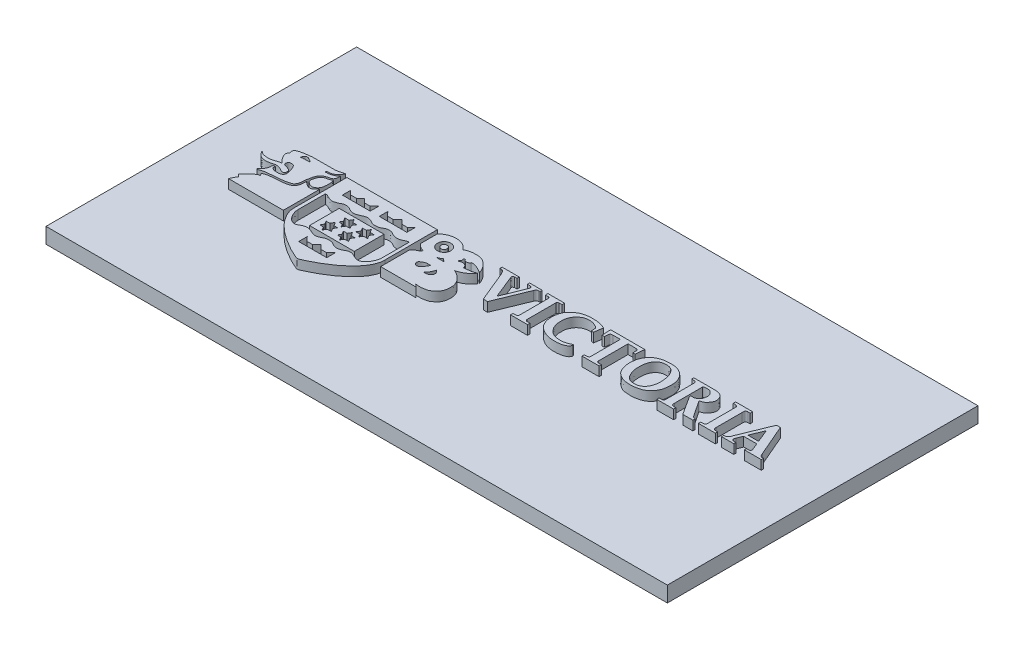
SolidWorks part; units mm, degrees
ref_plane "Front Plane" through (0, 0, 0) normal (0, 0, 1) x (1, 0, 0)
ref_plane "Top Plane" through (0, 0, 0) normal (0, 1, 0) x (1, 0, 0)
ref_plane "Right Plane" through (0, 0, 0) normal (1, 0, 0) x (0, 0, -1)
sketch "Sketch1" plane through (0, 0, 0) normal (0, 1, 0) x (1, 0, 0)
  line L1 (-100, 50) -> (100, 50)
  line L2 (-100, 50) -> (-100, -50)
  line L3 (-100, -50) -> (100, -50)
  line L4 (100, 50) -> (100, -50)
  dimension "D1" = 100
  dimension "D2" = 200
  dimension "D3" = 50
  dimension "D4" = 100
extrude "Boss-Extrude1" add sketch "Sketch1" along normal blind 5
sketch "Sketch3" plane through (0, 5, 0) normal (0, 1, 0) x (1, 0, 0)
  line L0 (337.3172, 310.4568) -> (1593.3172, 310.4568) construction
  line L2 (214, 281.56) -> (1470, 281.56) construction
sketch "Sketch4" plane through (0, 5, 0) normal (0, 1, 0) x (1, 0, 0)
sketch "Sketch5" plane through (0, 5, 0) normal (0, 1, 0) x (1, 0, 0)
  line L0 (-63.2832, 1.3739) -> (-63.2832, -10.3111)
  line L1 (-63.2832, -10.3111) -> (-80.9037, -10.3111)
  line L2 (-62.2093, 9.0496) -> (-33.087, 9.0496)
  line L3 (-33.087, 9.0496) -> (-33.087, -7.8265)
  line L4 (-62.2093, 9.0496) -> (-62.2093, -7.8265)
  line L5 (-52.1107, -16.5513) -> (-52.1107, -13.7896)
  line L6 (-52.1107, -13.7896) -> (-50.8663, -15.1704)
  line L7 (-50.8663, -15.1704) -> (-49.0633, -15.1704)
  line L8 (-49.0633, -15.1704) -> (-47.6668, -13.7739)
  line L9 (-47.6668, -13.7739) -> (-46.2702, -15.1704)
  line L10 (-46.2702, -15.1704) -> (-44.4842, -15.1704)
  line L11 (-44.4842, -15.1704) -> (-43.0876, -13.7739)
  line L12 (-43.0876, -13.7739) -> (-43.0876, -16.5513)
  line L13 (-43.0876, -16.5513) -> (-52.1107, -16.5513)
  line L14 (-51.5411, -5.2897) -> (-52.1934, -6.4621)
  line L15 (-53.3409, -8.5244) -> (-52.1596, -8.5244)
  line L16 (-49.6492, -8.5244) -> (-50.261, -7.4783)
  line L17 (-53.3409, -6.4621) -> (-52.1934, -6.4621)
  line L18 (-49.6492, -6.4621) -> (-50.261, -7.4783)
  line L19 (-51.5411, -9.6043) -> (-52.1596, -8.5244)
  line L20 (-50.8554, -6.4621) -> (-49.6492, -6.4621)
  line L21 (-52.7588, -7.4783) -> (-53.3409, -8.5244)
  line L22 (-52.7588, -7.4783) -> (-53.3409, -6.4621)
  line L23 (-50.8909, -8.5244) -> (-49.6492, -8.5244)
  line L24 (-50.8554, -6.4621) -> (-51.5411, -5.2897)
  line L25 (-50.8909, -8.5244) -> (-51.5411, -9.6043)
  line L26 (-47.8046, -6.4621) -> (-46.5759, -6.4621)
  line L27 (-44.1019, -6.4621) -> (-44.7111, -7.482)
  line L28 (-45.9533, -9.5616) -> (-46.5727, -8.5244)
  line L29 (-45.9533, -5.3563) -> (-46.5759, -6.4621)
  line L30 (-47.7371, -8.5244) -> (-46.5727, -8.5244)
  line L31 (-44.1019, -8.5244) -> (-44.7111, -7.482)
  line L32 (-45.307, -6.4621) -> (-44.1019, -6.4621)
  line L33 (-47.1721, -7.521) -> (-47.7371, -8.5244)
  line L34 (-47.1721, -7.521) -> (-47.8046, -6.4621)
  line L35 (-45.3338, -8.5244) -> (-44.1019, -8.5244)
  line L36 (-45.3338, -8.5244) -> (-45.9533, -9.5616)
  line L37 (-45.307, -6.4621) -> (-45.9533, -5.3563)
  line L38 (-49.3065, -1.5215) -> (-49.8917, -2.5463)
  line L39 (-51.0871, -4.64) -> (-49.9803, -4.64)
  line L40 (-47.4661, -4.64) -> (-48.0944, -3.5753)
  line L41 (-51.2589, -2.5463) -> (-49.8917, -2.5463)
  line L42 (-47.4661, -2.5463) -> (-48.0944, -3.5753)
  line L43 (-49.3625, -5.6517) -> (-49.9803, -4.64)
  line L44 (-48.7017, -2.5463) -> (-47.4661, -2.5463)
  line L45 (-50.5523, -3.7034) -> (-51.0871, -4.64)
  line L46 (-50.5523, -3.7034) -> (-51.2589, -2.5463)
  line L47 (-48.7446, -4.64) -> (-47.4661, -4.64)
  line L48 (-48.7446, -4.64) -> (-49.3625, -5.6517)
  line L49 (-48.7017, -2.5463) -> (-49.3065, -1.5215)
  line L50 (-45.6097, -4.64) -> (-44.975, -3.5824)
  line L51 (-43.7381, -1.5215) -> (-43.1103, -2.5463)
  line L52 (-41.8277, -4.64) -> (-43.1226, -4.64)
  line L53 (-45.6097, -2.5463) -> (-44.975, -3.5824)
  line L54 (-43.7187, -5.6332) -> (-43.1226, -4.64)
  line L55 (-41.866, -2.5463) -> (-43.1103, -2.5463)
  line L56 (-44.3272, -4.64) -> (-43.7187, -5.6332)
  line L57 (-44.3531, -2.5463) -> (-43.7381, -1.5215)
  line L58 (-44.3531, -2.5463) -> (-45.6097, -2.5463)
  line L59 (-42.4818, -3.5723) -> (-41.8277, -4.64)
  line L60 (-42.4818, -3.5723) -> (-41.866, -2.5463)
  line L61 (-44.3272, -4.64) -> (-45.6097, -4.64)
  line L62 (-34.1334, 1.0615) -> (-34.1334, -7.8265)
  line L63 (-54.827, -0.8011) -> (-40.4157, -0.8011)
  line L64 (-54.827, -0.8011) -> (-54.827, -10.3593)
  line L65 (-54.827, -10.3593) -> (-40.4157, -10.3593)
  line L66 (-40.4157, -0.8011) -> (-40.4157, -10.3593)
  line L67 (-61.1063, 1.0449) -> (-61.1063, -7.8265)
  line L68 (-58.0074, 3.4152) -> (-49.0633, 3.4152)
  line L69 (-49.0633, 3.4152) -> (-49.0633, 6.1619)
  line L70 (-49.0633, 6.1619) -> (-50.4367, 4.7885)
  line L71 (-50.4367, 4.7885) -> (-52.1934, 4.7885)
  line L72 (-52.1934, 4.7885) -> (-53.5353, 6.1305)
  line L73 (-53.5353, 6.1305) -> (-54.8773, 4.7885)
  line L74 (-54.8773, 4.7885) -> (-56.7252, 4.7885)
  line L75 (-56.7252, 4.7885) -> (-58.0074, 6.0706)
  line L76 (-58.0074, 6.0706) -> (-58.0074, 3.4152)
  line L77 (-46.1397, 6.1619) -> (-46.1397, 3.4152)
  line L78 (-46.1397, 3.4152) -> (-37.2605, 3.4152)
  line L79 (-37.2605, 3.4152) -> (-37.2605, 6.1619)
  line L80 (-37.2605, 6.1619) -> (-38.5572, 4.8651)
  line L81 (-38.5572, 4.8651) -> (-40.3517, 4.8651)
  line L82 (-40.3517, 4.8651) -> (-41.7001, 6.2135)
  line L83 (-41.7001, 6.2135) -> (-43.1103, 4.8033)
  line L84 (-43.1103, 4.8033) -> (-44.8724, 4.8033)
  line L85 (-44.8724, 4.8033) -> (-46.1397, 6.1619)
  line L86 (-31.9218, 7.7833) -> (-31.9218, 2.5651)
  line L87 (-31.9218, -10.3593) -> (-20.5485, -10.3593)
  line L88 (-31.9218, -0.9593) -> (-31.9218, -10.3593)
  line L89 (-25.5083, 1.1635) -> (-22.9705, 1.1635)
  line L90 (-25.2779, -1.9652) -> (-24.1564, -1.9652)
  line L91 (-12.2253, 9.0496) -> (-6.6902, 9.0496)
  line L92 (0.6832, 9.0496) -> (0.6832, 8.3375)
  line L93 (0.6832, 8.3375) -> (0.1855, 8.3375)
  line L94 (-12.2253, 8.3375) -> (-12.2253, 9.0496)
  line L95 (-6.6902, 9.0496) -> (-6.6902, 8.3375)
  line L96 (-3.3772, 9.0496) -> (-3.3772, 8.3375)
  line L97 (-3.3772, 9.0496) -> (0.6832, 9.0496)
  line L98 (-6.6902, 8.3375) -> (-7.4716, 8.3375)
  line L99 (-6.3278, -2.896) -> (-4.9619, -2.896)
  line L100 (-4.9619, -2.896) -> (-0.6788, 7.5455)
  line L101 (-6.3278, -2.896) -> (-10.4507, 7.0158)
  line L102 (-4.9331, 0.0557) -> (-2.014, 7.3165)
  line L103 (-4.9331, 0.0557) -> (-7.8598, 7.3165)
  line L104 (-11.6908, 8.3375) -> (-12.2253, 8.3375)
  line L105 (-2.3592, 8.3375) -> (-3.3772, 8.3375)
  line L106 (6.9917, -2.1108) -> (7.904, -2.1108)
  line L107 (6.8779, 8.242) -> (7.904, 8.242)
  line L108 (3.9499, -1.5215) -> (3.9499, 7.7833)
  line L109 (21.0472, 8.3851) -> (20.6035, 5.5732)
  line L110 (6.3721, -1.5215) -> (6.3721, 7.7833)
  line L111 (2.428, -2.896) -> (7.904, -2.896)
  line L112 (2.428, -2.896) -> (2.428, -2.1108)
  line L113 (2.428, -2.1108) -> (3.3607, -2.1108)
  line L114 (7.904, -2.896) -> (7.904, -2.1108)
  line L115 (2.5079, 9.0496) -> (7.904, 9.0496)
  line L116 (2.5079, 9.0496) -> (2.5079, 8.242)
  line L117 (2.5079, 8.242) -> (3.53, 8.242)
  line L118 (7.904, 9.0496) -> (7.904, 8.242)
  line L119 (20.6035, 5.5732) -> (19.925, 5.6803)
  line L120 (19.925, 5.6803) -> (19.8426, 7.0158)
  line L121 (26.9382, 7.9312) -> (24.5244, 7.9312)
  line L122 (25.4187, -2.896) -> (30.9293, -2.896)
  line L123 (25.4187, -2.896) -> (25.4187, -2.1826)
  line L124 (25.4187, -2.1826) -> (25.9053, -2.1826)
  line L125 (30.9293, -2.896) -> (30.9293, -2.1826)
  line L126 (49.4918, 9.0496) -> (49.4918, 8.3851)
  line L127 (29.4217, -1.5215) -> (29.4217, 7.9312)
  line L128 (29.9849, -2.1826) -> (30.9293, -2.1826)
  line L129 (26.9382, -1.5215) -> (26.9382, 7.9312)
  line L130 (29.4217, 7.9312) -> (31.9328, 7.9312)
  line L131 (22.6804, 9.0496) -> (33.7049, 9.0496)
  line L132 (22.6804, 9.0496) -> (22.8673, 6.1619)
  line L133 (22.8673, 6.1619) -> (23.6161, 6.1619)
  line L134 (33.7049, 9.0496) -> (33.4622, 6.1619)
  line L135 (33.4622, 6.1619) -> (32.7405, 6.1619)
  line L136 (49.4918, 9.0496) -> (56.4225, 9.0496)
  line L137 (53.4504, 7.8779) -> (53.4504, -1.1515)
  line L138 (51.0008, -1.2249) -> (51.0008, 7.1755)
  line L139 (57.8954, -2.92) -> (61.1428, -2.92)
  line L140 (49.5337, -2.92) -> (54.9326, -2.92)
  line L141 (49.5337, -2.92) -> (49.5337, -2.1826)
  line L142 (49.5337, -2.1826) -> (50.0195, -2.1826)
  line L143 (54.9326, -2.92) -> (54.9326, -2.1826)
  line L144 (61.1428, -2.92) -> (61.1428, -2.1826)
  line L145 (57.8954, -2.92) -> (54.1811, 2.8405)
  line L146 (57.0409, 2.9956) -> (60.0891, -1.5871)
  line L147 (54.1849, -2.1826) -> (54.9326, -2.1826)
  line L148 (67.6475, 8.2653) -> (68.3886, 8.2653)
  line L149 (62.9361, -2.92) -> (68.3886, -2.92)
  line L150 (62.9361, -2.92) -> (62.9361, -2.1826)
  line L151 (62.9361, -2.1826) -> (63.8006, -2.1826)
  line L152 (68.3886, -2.92) -> (68.3886, -2.1826)
  line L153 (62.9361, 9.0496) -> (68.3886, 9.0496)
  line L154 (62.9361, 9.0496) -> (62.9361, 8.2653)
  line L155 (62.9361, 8.2653) -> (63.6999, 8.2653)
  line L156 (68.3886, 9.0496) -> (68.3886, 8.2653)
  line L157 (67.3329, -2.1826) -> (68.3886, -2.1826)
  line L158 (64.4296, 7.1428) -> (64.4296, -1.2249)
  line L159 (75.871, 5.9878) -> (74.1921, 1.7526)
  line L160 (66.9175, 7.1428) -> (66.9175, -1.2249)
  line L161 (75.871, 5.9878) -> (77.6217, 1.7526)
  line L162 (74.1921, 1.7526) -> (77.6217, 1.7526)
  line L163 (73.8015, 0.7672) -> (78.0291, 0.7672)
  line L164 (77.7139, -2.896) -> (83.1232, -2.896)
  line L165 (77.7139, -2.896) -> (77.7139, -2.2065)
  line L166 (77.7139, -2.2065) -> (78.5421, -2.2065)
  line L167 (83.1232, -2.896) -> (83.1232, -2.2065)
  line L168 (74.2826, -2.896) -> (70.355, -2.896)
  line L169 (74.2826, -2.896) -> (74.2826, -2.2065)
  line L170 (74.2826, -2.2065) -> (73.4593, -2.2065)
  line L171 (70.355, -2.896) -> (70.355, -2.2065)
  line L172 (73.8015, 0.7672) -> (73.1172, -0.9593)
  line L173 (78.0291, 0.7672) -> (78.7977, -1.0923)
  line L174 (76.0075, 9.1296) -> (71.8933, -0.9593)
  line L175 (76.0075, 9.1296) -> (77.2609, 9.1296)
  line L176 (77.2609, 9.1296) -> (81.6634, -1.0923)
  line L177 (70.6873, -2.2065) -> (70.355, -2.2065)
  line L178 (82.7523, -2.2065) -> (83.1232, -2.2065)
  circle A0 centre (-27.1702, 5.3248) radius 2.1439
  circle A1 centre (-27.1725, 5.32) radius 0.9895
  spline S0 degree 3 poles (-63.6706, 9.4448) (-63.3718, 10.0323) (-63.8224, 9.7441) (-64.1106, 9.658) (-64.5317, 9.5574) (-64.9536, 9.4352) (-65.5434, 9.3039) (-66.2489, 9.2125) (-67.1417, 9.2449) (-68.1166, 9.2139) (-69.3679, 9.2331) (-70.6021, 9.2283) (-71.7021, 9.2222) (-72.38, 9.2465) (-73.2805, 9.2286) (-74.4285, 9.1224) (-75.7628, 8.8959) (-76.8244, 8.7102) (-77.5916, 8.4293) (-78.2655, 8.1228) (-78.4173, 7.525) (-78.4231, 7.0723) (-78.239, 6.8794) (-78.1623, 6.7454) (-78.3118, 6.6595) (-78.4554, 6.5414) (-78.5433, 6.3072) (-78.6223, 5.9835) (-78.7042, 5.6314) (-78.6102, 5.2628) (-78.421, 4.8656) (-78.1792, 4.4363) (-77.8669, 3.9347) (-77.5302, 3.4855) (-77.1961, 3.05) (-76.8585, 2.8263) (-76.7231, 2.6634) (-76.5926, 2.6155) (-76.6613, 2.4901) (-76.8004, 2.5711) (-77.0316, 2.5397) (-77.3623, 2.5504) (-77.7564, 2.3515) (-78.1822, 2.2824) (-78.5786, 2.0526) (-79.0593, 1.9753) (-79.6046, 1.7731) (-80.2467, 1.8029) (-80.9206, 1.7931) (-81.4923, 1.8929) (-81.9854, 1.9805) (-82.3592, 2.1503) (-82.6619, 2.3503) (-82.9235, 2.5204) (-83.0259, 2.674) (-83.2103, 2.6978) (-83.1557, 2.5832) (-83.1628, 2.4687) (-83.0084, 2.3856) (-82.9197, 2.2156) (-82.7477, 2.0038) (-82.5121, 1.7498) (-82.2373, 1.4596) (-81.9494, 1.1662) (-81.6102, 1.015) (-81.3149, 0.8302) (-81.0063, 0.7701) (-80.7026, 0.7134) (-80.2979, 0.6377) (-79.72, 0.6349) (-78.9764, 0.7316) (-78.2307, 0.9037) (-77.5321, 1.1317) (-76.8334, 1.2022) (-76.2147, 1.0617) (-75.6858, 0.8931) (-75.2703, 0.6717) (-74.8218, 0.5045) (-74.4906, 0.2282) (-74.1206, 0.2274) (-73.6937, 0.2483) (-73.32, 0.8418) (-73.4364, 1.5648) (-73.9671, 1.9701) (-74.4947, 2.1984) (-75.0734, 2.3775) (-75.5109, 2.4247) (-75.8343, 2.5506) (-75.8972, 2.8252) (-76.0668, 3.0828) (-75.9996, 3.4674) (-75.8109, 3.846) (-75.2643, 4.079) (-74.5597, 4.1038) (-73.9506, 3.6248) (-73.6958, 3.0814) (-73.4593, 2.6057) (-73.3209, 2.1079) (-73.1415, 1.5844) (-73.0101, 0.958) (-72.9178, 0.3049) (-73.2253, -0.2651) (-73.6609, -0.5853) (-74.146, -0.7714) (-74.7635, -0.7158) (-75.3751, -0.7643) (-76.0386, -0.7032) (-76.4438, -0.4071) (-76.7846, -0.1747) (-76.7884, 0.1878) (-76.7872, 0.3729) (-76.7135, 0.6925) (-76.8859, 0.6075) (-77.0381, 0.6636) (-77.2079, 0.4964) (-77.4832, 0.4748) (-77.4723, 0.1777) (-77.5399, -0.0388) (-77.4886, -0.3724) (-77.5938, -0.7179) (-77.7078, -1.1194) (-77.9059, -1.4515) (-78.0752, -1.8108) (-78.3481, -2.0976) (-78.6376, -2.3554) (-78.8543, -2.5878) (-79.0395, -2.7039) (-79.1757, -2.8205) (-79.1047, -2.9496) (-79.025, -3.0423) (-78.9496, -3.2344) (-78.768, -3.1279) (-78.5675, -2.9739) (-78.1953, -2.8523) (-77.7677, -2.7045) (-77.3061, -2.6128) (-76.7831, -2.4869) (-76.2187, -2.4464) (-75.674, -2.4493) (-75.222, -2.3394) (-74.7388, -2.3235) (-74.2383, -2.2934) (-73.6227, -2.2026) (-72.9651, -2.1918) (-72.3122, -2.1372) (-71.7565, -2.007) (-71.2434, -1.9801) (-70.6847, -1.8447) (-70.1301, -1.7602) (-69.6287, -1.5382) (-69.2229, -1.4205) (-68.8402, -1.2415) (-68.6692, -0.8429) (-68.3947, -0.4745) (-68.3325, 0.0606) (-68.2247, 0.599) (-68.2337, 1.2042) (-68.1461, 1.7732) (-68.0586, 2.333) (-67.924, 2.8923) (-67.8396, 3.4214) (-67.7102, 3.8767) (-67.532, 4.239) (-67.3638, 4.6328) (-67.1583, 5.0416) (-66.8452, 5.3692) (-66.5207, 5.6633) (-66.0804, 5.7498) (-65.697, 5.9232) (-65.2665, 6.1002) (-64.7761, 6.1471) (-64.2324, 6.2996) (-63.875, 6.6468) (-63.6327, 6.9856) (-63.6388, 7.2947) (-63.61, 7.6504) (-63.5993, 8.0057) (-63.6137, 8.254) (-63.5856, 8.5309) (-63.7106, 8.236) (-63.9046, 8.2109) (-64.0231, 7.9768) (-64.2629, 7.8857) (-64.4912, 7.7113) (-64.7507, 7.5771) (-65.0483, 7.4733) (-65.355, 7.3417) (-65.7827, 7.2605) (-66.263, 7.0994) (-66.7007, 7.1891) (-67.2051, 7.0007) (-67.2184, 7.2862) (-67.3029, 7.5123) (-67.0374, 7.5417) (-66.8004, 7.5464) (-66.4258, 7.5558) (-65.9621, 7.6034) (-65.4663, 7.77) (-64.9507, 7.9828) (-64.496, 8.3379) (-64.1421, 8.7264) (-63.7833, 9.1184) (-63.6706, 9.4448) (-63.3718, 10.0323) (-63.8224, 9.7441) knots -0.014185 -0.009524 -0.004487 0 0.002922 0.007539 0.0116 0.016663 0.022127 0.031401 0.03996 0.051439 0.06346 0.081084 0.092009 0.099613 0.103371 0.121612 0.137382 0.148009 0.156662 0.1649 0.170068 0.176303 0.178127 0.179109 0.180646 0.182572 0.185575 0.188395 0.193718 0.197078 0.20067 0.208181 0.213256 0.22008 0.226624 0.231275 0.232858 0.234021 0.234684 0.23647 0.237953 0.242567 0.246967 0.252213 0.256585 0.261791 0.268075 0.275492 0.28261 0.290249 0.294501 0.29903 0.303572 0.306549 0.308991 0.30988 0.310933 0.311838 0.313733 0.31576 0.318203 0.322632 0.327162 0.331379 0.335974 0.33925 0.342736 0.346169 0.349446 0.356242 0.365044 0.374057 0.381349 0.389192 0.396754 0.402019 0.407414 0.412151 0.417809 0.420748 0.424104 0.43135 0.440272 0.445602 0.452535 0.459246 0.465251 0.467345 0.469841 0.473834 0.477184 0.48207 0.487098 0.495833 0.504005 0.510781 0.515484 0.521435 0.527715 0.533623 0.542618 0.548476 0.553868 0.560182 0.56501 0.573976 0.580616 0.585997 0.590652 0.592855 0.597017 0.598746 0.599916 0.601641 0.603847 0.607079 0.608707 0.612535 0.614729 0.619537 0.624176 0.628433 0.632179 0.637175 0.641232 0.645058 0.647286 0.648926 0.649814 0.651599 0.65348 0.65488 0.657243 0.662387 0.667208 0.672259 0.677792 0.684879 0.690797 0.695624 0.700067 0.70665 0.712104 0.72049 0.728245 0.733585 0.739203 0.745057 0.752456 0.757539 0.762931 0.766528 0.770805 0.776606 0.781425 0.788128 0.79472 0.801188 0.807028 0.81334 0.820079 0.824633 0.828827 0.833315 0.838747 0.843692 0.848197 0.85278 0.858073 0.862077 0.867963 0.874237 0.880099 0.884094 0.887402 0.889917 0.896037 0.898077 0.899803 0.901494 0.904398 0.906399 0.909346 0.912507 0.91586 0.918877 0.92288 0.926746 0.933307 0.938472 0.943323 0.944279 0.947417 0.948706 0.951838 0.955752 0.960795 0.96717 0.972831 0.979077 0.985815 0.990476 0.995513 1 1.002922 1.007539 1.0116 only from (-63.5013, 9.9128) to (-63.5013, 9.9128)
  spline S1 degree 3 poles (-72.7524, 7.4273) (-72.2913, 7.4158) (-72.6377, 7.6218) (-72.8252, 7.7209) (-73.0325, 7.8835) (-73.2478, 8.0165) (-73.4666, 8.1259) (-73.6658, 8.2462) (-73.9046, 8.3593) (-74.2256, 8.3951) (-74.5037, 8.3868) (-74.7093, 8.2877) (-74.7654, 8.1508) (-74.8912, 8.0572) (-74.9627, 7.9286) (-75.0789, 7.8339) (-75.1684, 7.7017) (-75.234, 7.5557) (-75.3336, 7.4478) (-75.4104, 7.3452) (-75.3771, 7.2342) (-75.2386, 7.1995) (-75.0792, 7.2969) (-74.8417, 7.2459) (-74.6264, 7.3362) (-74.3799, 7.3003) (-74.157, 7.3641) (-73.9429, 7.352) (-73.7083, 7.3501) (-73.4136, 7.3891) (-73.0241, 7.4096) (-72.7524, 7.4273) (-72.2913, 7.4158) (-72.6377, 7.6218) knots -0.149458 -0.090668 -0.035242 0 0.039164 0.070643 0.110335 0.149929 0.183646 0.217874 0.252957 0.299065 0.359185 0.373353 0.396408 0.420492 0.441198 0.460153 0.485908 0.511107 0.529784 0.551688 0.562871 0.57424 0.60834 0.63974 0.676149 0.707437 0.747195 0.776545 0.801657 0.850542 0.909332 0.964758 1 1.039164 1.070643 1.110335 only from (-72.4191, 7.4501) to (-72.4191, 7.4501)
  spline S2 degree 3 poles (-63.2478, 3.7242) (-63.2965, 3.2753) (-63.3976, 2.7685) (-63.5011, 2.1147) (-63.8871, 1.6002) (-64.314, 1.1985) (-64.7542, 0.911) (-65.2296, 0.8656) (-65.6626, 0.9204) (-66.1081, 1.0275) (-66.5261, 1.2253) (-66.7087, 1.6265) (-67.1152, 1.6834) (-67.1247, 1.9535) (-67.2336, 2.1637) (-67.3057, 2.4504) (-67.3089, 2.775) (-67.215, 3.1405) (-67.1146, 3.5892) (-66.9174, 4.1259) (-66.622, 4.7065) (-66.1437, 5.1053) (-65.7055, 5.3829) (-65.2609, 5.4804) (-64.8093, 5.5636) (-64.3156, 5.6844) (-63.9543, 5.8977) (-63.7339, 6.0588) (-63.5383, 6.0834) (-63.5053, 5.9424) (-63.4566, 5.8013) (-63.3783, 5.617) (-63.3174, 5.351) (-63.2797, 5.0299) (-63.2488, 4.6084) (-63.2697, 4.1439) (-63.2478, 3.7242) (-63.2965, 3.2753) (-63.3976, 2.7685) knots -0.084958 -0.047218 -0.015732 0 0.044096 0.089564 0.131588 0.170952 0.209251 0.234748 0.265922 0.297281 0.32841 0.354679 0.382263 0.391291 0.405431 0.430314 0.450299 0.470578 0.506489 0.543452 0.586454 0.63649 0.667578 0.690426 0.727926 0.761067 0.792777 0.811427 0.817761 0.827466 0.83477 0.849638 0.867184 0.890133 0.915042 0.952782 0.984268 1 1.044096 1.089564 1.131588 only from (-63.2832, 3.4152) to (-63.2832, 3.4152)
  spline S3 degree 3 poles (-80.9037, -10.3111) (-80.8567, -9.8883) (-80.4008, -9.3627) (-80.1575, -8.5943) (-79.9112, -8.3088) (-79.781, -8.1535) (-79.9911, -7.9968) (-80.1622, -7.8273) (-80.3811, -7.6817) (-80.6153, -7.4567) (-80.3898, -7.3105) (-80.3006, -7.1038) (-80.0606, -6.9479) (-79.9395, -6.6588) (-79.6835, -6.4331) (-79.4161, -6.2251) (-79.1784, -5.9098) (-78.8323, -5.6212) (-78.4789, -5.3537) (-78.1863, -5.0576) (-77.9029, -4.8479) (-77.6121, -4.6502) (-77.309, -4.4565) (-76.9584, -4.3576) (-76.7365, -4.3907) (-76.4994, -4.3139) (-76.6744, -4.2228) (-76.7825, -4.1113) (-76.9514, -3.9611) (-76.9811, -3.7815) (-77.1087, -3.6916) (-76.9842, -3.5535) (-76.8213, -3.491) (-76.642, -3.3019) (-76.3561, -3.2444) (-76.0456, -3.1404) (-75.6409, -3.0381) (-75.1399, -2.9512) (-74.5597, -2.9413) (-74.0506, -2.829) (-73.5877, -2.8694) (-73.1308, -2.7526) (-72.5295, -2.7099) (-71.866, -2.6805) (-71.2282, -2.6573) (-70.6506, -2.529) (-70.0664, -2.476) (-69.4157, -2.2628) (-68.7613, -2.0346) (-68.1648, -1.5391) (-67.8773, -0.9007) (-67.6785, -0.2629) (-67.6049, 0.426) (-67.599, 1.0269) (-67.5734, 1.366) (-67.5846, 1.5357) (-67.4448, 1.4319) (-67.4234, 1.2999) (-67.2747, 1.1232) (-67.0679, 1.026) (-66.9013, 0.8157) (-66.6661, 0.6653) (-66.382, 0.4845) (-66.0958, 0.3135) (-65.7712, 0.2147) (-65.4504, 0.1293) (-65.0772, 0.0914) (-64.7041, 0.2057) (-64.3631, 0.4536) (-64.0278, 0.7442) (-63.6906, 1) (-63.4748, 1.2443) (-63.3847, 1.4243) (-63.2832, 1.3739) knots 0 0 0 0 0.044728 0.076096 0.084621 0.088722 0.095225 0.107117 0.117598 0.126321 0.134191 0.140594 0.151686 0.163924 0.17421 0.188942 0.20132 0.217532 0.238556 0.250302 0.263444 0.277472 0.289076 0.303608 0.314612 0.318389 0.322851 0.328774 0.338724 0.345325 0.348718 0.352735 0.361179 0.369737 0.379905 0.392591 0.406163 0.425962 0.448676 0.470164 0.483089 0.499515 0.521778 0.549655 0.573044 0.592108 0.614944 0.637596 0.667615 0.69105 0.720933 0.743474 0.764603 0.798328 0.805065 0.80813 0.811613 0.817581 0.824422 0.835458 0.842573 0.853559 0.866046 0.879965 0.890147 0.903404 0.916741 0.931013 0.945346 0.963028 0.980302 0.991499 1 1 1 1
  spline S4 degree 3 poles (-62.2093, -7.8265) (-62.2236, -8.4206) (-62.1477, -9.3577) (-61.7046, -10.4058) (-61.4159, -11.0721) (-61.0854, -11.5903) (-60.8199, -12.1621) (-60.3695, -12.6466) (-60.0592, -13.1622) (-59.6538, -13.5763) (-59.3575, -14.0525) (-58.8903, -14.4001) (-58.5523, -14.8081) (-58.1352, -15.1382) (-57.7374, -15.5322) (-57.3129, -15.9578) (-56.7412, -16.3863) (-56.111, -16.8373) (-55.4155, -17.3659) (-54.7031, -17.8936) (-53.8743, -18.356) (-52.9944, -18.9472) (-52.0138, -19.5052) (-50.9185, -20.1326) (-49.7154, -20.7145) (-48.618, -21.1567) (-47.9175, -21.5028) (-47.2519, -21.5014) (-46.6167, -21.1803) (-45.7436, -20.7565) (-44.8865, -20.3944) (-43.8391, -19.7851) (-42.729, -19.2821) (-41.8221, -18.619) (-41.0622, -18.1857) (-40.2556, -17.5904) (-39.1585, -17.0005) (-38.363, -16.1443) (-37.565, -15.5895) (-36.989, -15.097) (-36.4887, -14.4485) (-35.8196, -13.9484) (-35.3312, -13.2519) (-34.8413, -12.6406) (-34.3813, -12.0282) (-34.0399, -11.3932) (-33.729, -10.7605) (-33.4783, -10.2118) (-33.1685, -9.254) (-33.0408, -8.4645) (-33.087, -7.8265) knots 0 0 0 0 0.042745 0.065588 0.081029 0.094527 0.109446 0.125721 0.141363 0.1522 0.166974 0.180921 0.193282 0.204652 0.218792 0.233277 0.247519 0.269744 0.288662 0.309937 0.332989 0.356357 0.38563 0.413535 0.446608 0.480613 0.499341 0.500191 0.528083 0.547672 0.570277 0.594254 0.634235 0.656911 0.674293 0.696649 0.728481 0.762545 0.779125 0.797872 0.816418 0.837311 0.856851 0.876739 0.893395 0.91144 0.928114 0.943802 0.954451 1 1 1 1
  spline S5 degree 3 poles (-61.1063, 1.0449) (-60.5501, 1.0784) (-59.8319, 0.6573) (-58.8029, 0.1727) (-57.7718, 0.0301) (-56.8994, 0.382) (-56.1242, 0.6529) (-55.4948, 1.0872) (-54.708, 1.1919) (-53.9333, 1.1263) (-53.3134, 0.932) (-52.8598, 0.6157) (-52.3742, 0.4155) (-51.9294, 0.1449) (-51.3052, 0.0989) (-50.6169, 0.1638) (-49.8855, 0.406) (-49.2293, 0.7265) (-48.6204, 1.0158) (-47.9903, 1.1908) (-47.251, 1.1993) (-46.5269, 0.9284) (-45.8328, 0.6845) (-45.262, 0.2171) (-44.5751, 0.1623) (-43.8416, 0.159) (-43.0793, 0.2777) (-42.3561, 0.6359) (-41.7456, 1.0801) (-41.0397, 1.1797) (-40.3035, 1.1996) (-39.4319, 0.9433) (-38.6547, 0.4163) (-37.883, 0.2362) (-37.0669, 0.1356) (-36.2198, 0.291) (-35.2131, 0.7573) (-34.5746, 1.1017) (-34.1334, 1.0615) knots 0 0 0 0 0.055544 0.086294 0.120049 0.161438 0.18333 0.206677 0.240875 0.264007 0.28875 0.308188 0.32187 0.344146 0.361977 0.386586 0.416899 0.442464 0.463659 0.48789 0.510902 0.540214 0.568664 0.588122 0.616068 0.638165 0.66622 0.696147 0.722721 0.744306 0.769848 0.800196 0.838188 0.867734 0.882609 0.924853 0.955795 1 1 1 1
  spline S6 degree 3 poles (-61.1063, -7.8265) (-61.1289, -8.5674) (-60.7667, -9.4286) (-60.285, -10.5221) (-59.789, -11.1229) (-59.2354, -11.8155) (-58.4762, -12.1457) (-57.6683, -12.3554) (-56.8734, -12.0576) (-56.1522, -11.5758) (-55.349, -11.3004) (-54.465, -11.1844) (-53.649, -11.3664) (-52.9496, -11.6709) (-52.3596, -11.9823) (-51.7339, -12.2396) (-50.6796, -12.322) (-49.6673, -11.8878) (-48.6189, -11.2974) (-47.8268, -11.239) (-47.0239, -11.2652) (-46.353, -11.4594) (-45.741, -11.8355) (-45.12, -12.1156) (-44.3969, -12.3388) (-43.5532, -12.2654) (-42.8228, -11.9688) (-42.1076, -11.5568) (-41.4157, -11.2476) (-40.6207, -11.1574) (-39.8865, -11.3704) (-39.0635, -11.677) (-38.2646, -12.2038) (-37.3268, -12.2721) (-36.2779, -12.0232) (-35.4456, -11.1979) (-34.567, -9.7894) (-34.1462, -8.6445) (-34.1334, -7.8265) knots 0 0 0 0 0.062934 0.084535 0.106498 0.132747 0.162843 0.178971 0.206403 0.234812 0.257469 0.281816 0.31405 0.330893 0.350298 0.374038 0.390983 0.443874 0.469083 0.498456 0.513281 0.541385 0.55968 0.577665 0.602553 0.626637 0.651997 0.672745 0.700875 0.71937 0.743228 0.768474 0.798424 0.82743 0.849989 0.893563 0.927222 1 1 1 1
  spline S7 degree 3 poles (-31.9218, -0.9593) (-31.6827, -0.7301) (-31.246, -0.3733) (-30.579, 0.0125) (-30.0261, 0.2202) (-29.7532, 0.5496) (-29.5244, 0.8605) (-29.816, 1.1026) (-30.1715, 1.1253) (-30.6855, 1.3309) (-31.2874, 1.8254) (-31.7983, 2.1957) (-31.9218, 2.5651) knots 0 0 0 0 0.167261 0.280115 0.391311 0.448966 0.506303 0.545037 0.608248 0.687789 0.81665 1 1 1 1
  spline S8 degree 3 poles (-20.5485, -10.3593) (-20.6902, -10.153) (-21.0282, -9.7913) (-21.3251, -9.6912) (-21.4986, -9.5496) (-21.3853, -9.5674) (-21.1856, -9.5447) (-20.8045, -9.6849) (-20.2812, -9.6794) (-19.7618, -9.6853) (-19.2394, -9.6324) (-18.7087, -9.5561) (-18.1172, -9.4356) (-17.3781, -9.23) (-16.623, -8.6643) (-15.8441, -8.1177) (-15.3913, -7.3648) (-15.0812, -6.6705) (-14.8772, -5.8625) (-14.8718, -4.9414) (-14.8152, -4.063) (-15.0548, -3.3394) (-15.3464, -2.5901) (-15.8851, -1.7947) (-16.632, -0.9424) (-17.4163, -0.3561) (-18.1959, 0.1156) (-18.701, 0.3352) (-19.0154, 0.403) knots 0 0 0 0 0.047312 0.065556 0.068887 0.072241 0.077913 0.108648 0.132674 0.167072 0.195288 0.2208 0.256954 0.296852 0.347895 0.413975 0.454077 0.493308 0.541711 0.592299 0.647967 0.68735 0.718816 0.782884 0.847049 0.908355 0.946211 1 1 1 1
  spline S9 degree 3 poles (-19.0154, 0.403) (-17.1953, 0.7871) (-15.5276, 1.8906) (-14.4786, 3.4453) knots 0 0 0 0 1 1 1 1
  spline S10 degree 3 poles (-14.4786, 3.4453) (-14.9981, 3.1676) (-15.8401, 2.8866) (-17.1676, 2.7686) (-17.9012, 2.6174) (-18.3619, 2.6354) knots 0 0 0 0 0.442148 0.655071 1 1 1 1
  spline S11 degree 3 poles (-18.3619, 2.6354) (-18.2774, 3.049) (-18.6859, 3.6568) (-19.5649, 3.9885) (-20.3298, 4.0186) (-20.6898, 3.5888) (-21.0651, 3.7143) (-20.9021, 4.0977) (-20.5823, 4.34) (-20.6245, 4.7712) (-20.7737, 5.1259) (-20.4836, 5.3113) (-20.1777, 5.2477) (-20.1142, 4.9108) (-19.6434, 4.7441) (-19.1128, 4.7598) (-18.6333, 4.9305) (-18.3004, 5.155) (-18.4057, 5.435) (-18.1833, 5.4147) (-17.8595, 5.3581) (-17.1977, 5.2553) (-15.9445, 4.8275) (-14.9557, 4.2955) (-14.3237, 3.8033) knots 0 0 0 0 0.095705 0.157407 0.231165 0.262504 0.28132 0.304328 0.341481 0.379412 0.400923 0.425807 0.445368 0.468278 0.498049 0.556339 0.59657 0.627464 0.639448 0.645271 0.672698 0.729116 0.803292 1 1 1 1
  spline S12 degree 3 poles (-14.3237, 3.8033) (-14.4843, 4.3953) (-14.8752, 5.2698) (-15.621, 6.3128) (-16.3626, 7.0826) (-17.2666, 7.7936) (-18.4945, 8.3523) (-19.8926, 8.4024) (-21.2279, 8.3553) (-22.3715, 8.0254) (-23.0713, 7.807) (-23.3423, 7.5455) knots 0 0 0 0 0.161629 0.250596 0.337393 0.443078 0.553128 0.686657 0.807763 0.904498 1 1 1 1
  spline S13 degree 3 poles (-23.3423, 7.5455) (-23.6729, 8.0291) (-24.4266, 8.7652) (-25.8253, 9.5128) (-27.3683, 9.7048) (-29.037, 9.609) (-30.6569, 8.9557) (-31.5401, 8.2012) (-31.9218, 7.7833) knots 0 0 0 0 0.178613 0.318982 0.477008 0.64791 0.826705 1 1 1 1
  spline S14 degree 3 poles (-22.9705, 1.1635) (-23.3384, 1.4473) (-23.855, 1.627) (-24.0564, 2.0868) knots 0 0 0 0 1 1 1 1
  spline S15 degree 3 poles (-25.5083, 1.1635) (-25.0476, 1.4135) (-24.3109, 1.5458) (-24.0564, 2.0868) knots 0 0 0 0 1 1 1 1
  spline S16 degree 3 poles (-24.1564, -1.9652) (-24.4272, -2.4665) (-24.8276, -3.2058) (-25.4823, -4.071) (-26.2529, -4.4203) (-27.0511, -4.1641) (-27.8885, -2.748) (-25.6459, -1.9609) (-25.2779, -1.9652) knots 0 0 0 0 0.228004 0.340633 0.428133 0.550141 0.644083 1 1 1 1
  spline S17 degree 3 poles (-23.4871, -4.9698) (-22.7229, -4.2875) (-22.1152, -3.357) (-21.9861, -2.3241) knots 0 0 0 0 1 1 1 1
  spline S18 degree 3 poles (-21.9861, -2.3241) (-21.6582, -2.6217) (-20.9215, -3.3059) (-21.5682, -4.8706) (-22.7754, -5.0962) (-23.4871, -4.9698) knots 0 0 0 0 0.33422 0.506124 1 1 1 1
  spline S19 degree 3 poles (-7.8598, 7.3165) (-7.9335, 7.4608) (-8.202, 7.8964) (-7.8347, 8.2372) (-7.6237, 8.2948) (-7.4716, 8.3375) knots 0 0 0 0 0.528889 0.668401 1 1 1 1
  spline S20 degree 3 poles (-10.4507, 7.0158) (-10.7495, 7.4713) (-11.017, 8.2966) (-11.6908, 8.3375) knots 0 0 0 0 1 1 1 1
  spline S21 degree 3 poles (-0.6788, 7.5455) (-0.5578, 7.9299) (-0.253, 8.3131) (0.1855, 8.3375) knots 0 0 0 0 1 1 1 1
  spline S22 degree 3 poles (-2.014, 7.3165) (-1.8137, 7.6551) (-1.8876, 8.2604) (-2.3592, 8.3375) knots 0 0 0 0 1 1 1 1
  spline S23 degree 2 poles (3.9499, 7.7833) (3.9032, 8.1404) (3.53, 8.242) knots 0 0 0 1 1 1
  spline S24 degree 2 poles (6.3721, 7.7833) (6.4978, 8.1373) (6.8779, 8.242) knots 0 0 0 1 1 1
  spline S25 degree 2 poles (3.9499, -1.5215) (3.9093, -2.033) (3.3607, -2.1108) knots 0 0 0 1 1 1
  spline S26 degree 2 poles (6.3721, -1.5215) (6.4651, -2.1523) (7.1524, -2.1108) knots 0 0 0 1 1 1
  spline S27 degree 3 poles (20.9916, -1.3889) (20.842, -1.6545) (20.6487, -2.2408) (19.8763, -2.5604) (19.1296, -2.9208) (18.1069, -3.0735) (16.8337, -3.1835) (15.4517, -3.0946) (14.1017, -2.8376) (12.9563, -2.354) (11.8779, -1.6757) (10.8736, -0.8818) (10.2126, 0.2627) (9.7014, 1.726) (9.5938, 3.3676) (9.8119, 4.8736) (10.2593, 6.3013) (11.2978, 7.4125) (12.4313, 8.2926) (13.4117, 8.8499) (14.4153, 9.0366) (15.5241, 9.2901) (16.7778, 9.2861) (18.0424, 9.287) (19.5004, 9.0017) (20.4688, 8.707) (21.0472, 8.3851) knots 0 0 0 0 0.031887 0.053209 0.078851 0.113611 0.15315 0.20434 0.248698 0.28726 0.325282 0.373718 0.410568 0.453084 0.524992 0.568837 0.602077 0.669992 0.712556 0.74348 0.779132 0.811792 0.854794 0.901392 0.935448 1 1 1 1
  spline S28 degree 3 poles (19.8426, 7.0158) (19.5912, 7.4061) (19.0038, 7.688) (18.1485, 8.072) (17.418, 8.2611) (16.5422, 8.3121) (15.6703, 8.2221) (14.8851, 8.0183) (14.2554, 7.6178) (13.5552, 7.131) (12.8167, 6.0478) (12.2714, 4.7756) (12.3216, 3.4091) (12.2801, 2.3205) (12.6245, 1.3579) (12.9101, 0.4754) (13.5644, -0.3626) (14.3175, -1.2011) (15.4677, -1.7119) (16.6998, -2.0305) (18.2669, -2.0173) (19.5844, -1.6859) (20.3834, -1.292) (20.6574, -1.1211) (20.7677, -1.0734) (20.9503, -1.1563) (20.9478, -1.3172) (20.9916, -1.3889) knots 0 0 0 0 0.056871 0.082978 0.121505 0.153621 0.195996 0.234795 0.256885 0.292271 0.344149 0.424447 0.465429 0.520131 0.563676 0.596577 0.639361 0.699952 0.73974 0.800095 0.863638 0.940377 0.973879 0.978106 0.982409 0.988882 1 1 1 1
  spline S29 degree 3 poles (31.9328, 7.9312) (32.0979, 7.9034) (32.4851, 7.9084) (32.7081, 7.4399) (32.6899, 6.8829) (32.6876, 6.4339) (32.7405, 6.1619) knots 0 0 0 0 0.260711 0.402943 0.634784 1 1 1 1
  spline S30 degree 3 poles (24.5244, 7.9312) (24.3668, 7.895) (23.7791, 7.9547) (23.6487, 7.0567) (23.6202, 6.6182) (23.6161, 6.1619) knots 0 0 0 0 0.298093 0.492106 1 1 1 1
  spline S31 degree 3 poles (29.4217, -1.5215) (29.3673, -1.8553) (29.6663, -2.1516) (29.9849, -2.1826) knots 0 0 0 0 1 1 1 1
  spline S32 degree 3 poles (26.9382, -1.5215) (27.0451, -2.1065) (26.2126, -2.187) (25.8503, -2.1826) knots 0 0 0 0 1 1 1 1
  spline S33 degree 3 poles (42.7953, -2.1223) (41.3686, -2.2347) (40.089, -2.0457) (38.815, -1.2118) (38.1501, 0.1744) (37.6598, 1.647) (37.5787, 3.0319) (37.6056, 4.6717) (38.0129, 6.2698) (38.9981, 7.6461) (40.2123, 8.2173) (41.6157, 8.3375) (42.9217, 8.1662) (43.839, 7.3394) (44.5285, 6.4342) (44.95, 5.3367) (45.223, 3.883) (45.3192, 2.4906) (45.1824, 1.0632) (44.7736, -0.1221) (44.0741, -1.3136) (42.7953, -2.1223) (41.3686, -2.2347) (40.089, -2.0457) knots -0.146989 -0.103666 -0.048068 0 0.040798 0.082882 0.150348 0.193367 0.242209 0.291497 0.361938 0.407683 0.461018 0.492791 0.552886 0.588352 0.616456 0.669523 0.706795 0.768363 0.812207 0.853011 0.896334 0.951932 1 1.040798 1.082882 1.150348 only from (41.2995, -2.1826) to (41.2995, -2.1826)
  spline S34 degree 3 poles (43.3946, 9.2652) (41.6057, 9.3299) (39.8878, 9.1958) (38.6073, 8.8076) (37.6196, 8.3466) (36.6779, 7.64) (35.9677, 6.727) (35.443, 5.7605) (35.1803, 4.9043) (34.9896, 3.74) (34.8939, 2.2826) (35.2832, 0.5117) (35.9989, -1.2089) (37.415, -2.2584) (38.756, -2.9764) (40.0944, -3.0455) (41.5782, -3.2251) (43.2566, -2.9217) (45.0396, -2.4587) (46.4452, -1.2554) (47.5709, 0.3985) (47.919, 2.4633) (47.9288, 4.5481) (47.3686, 6.3265) (46.3618, 7.777) (45.0758, 8.6685) (43.3946, 9.2652) (41.6057, 9.3299) (39.8878, 9.1958) knots -0.130302 -0.087916 -0.056011 0 0.042236 0.070444 0.098053 0.122136 0.156435 0.182312 0.202782 0.222023 0.269246 0.308974 0.355246 0.402311 0.435517 0.465532 0.499654 0.545316 0.590207 0.633192 0.678323 0.734955 0.784051 0.831143 0.869698 0.912084 0.943989 1 1.042236 1.070444 1.098053 only from (41.4215, 9.287) to (41.4215, 9.287)
  spline S35 degree 3 poles (51.0008, -1.2249) (50.9547, -1.4315) (51.0267, -2.1854) (50.22, -2.1249) (50.0195, -2.1826) knots 0 0 0 0 0.476664 1 1 1 1
  spline S36 degree 3 poles (53.4504, -1.1515) (53.4334, -1.4215) (53.5165, -2.132) (54.1829, -2.1983) (54.3913, -2.1826) knots 0 0 0 0 0.571006 1 1 1 1
  spline S37 degree 3 poles (61.1428, -2.1826) (60.7128, -2.1978) (60.323, -1.9288) (60.0891, -1.5871) knots 0 0 0 0 1 1 1 1
  spline S38 degree 3 poles (56.4225, 9.0496) (56.9047, 8.9985) (57.6673, 8.9692) (58.4115, 8.4868) (58.8987, 8.0949) (59.2176, 7.4968) (59.4952, 6.6778) (59.4343, 5.6717) (58.9037, 4.8689) (58.3309, 4.1007) (57.6043, 3.6657) (57.0593, 3.5678) (56.6636, 3.4017) (57.0105, 3.0154) (57.0409, 2.9956) knots 0 0 0 0 0.162551 0.232353 0.285066 0.363759 0.44739 0.565319 0.674093 0.753999 0.877664 0.929456 0.944096 1 1 1 1
  spline S39 degree 3 poles (53.4504, 7.8779) (53.4877, 8.0392) (53.8251, 8.1599) (54.4348, 8.22) (55.0616, 8.1333) (55.7246, 8.0853) (55.9938, 7.7131) (56.2604, 7.5189) (56.4387, 7.3483) (56.5942, 7.1072) (56.798, 6.7875) (56.7865, 6.3719) (56.9515, 5.9705) (56.7852, 5.5575) (56.8073, 5.082) (56.5514, 4.6498) (56.2816, 4.1498) (55.7322, 3.7926) (55.2282, 3.4911) (54.7891, 3.5219) (54.5049, 3.4965) (54.231, 3.5615) (54.076, 3.4547) (53.9883, 3.3655) (54.0251, 3.1282) (54.0439, 2.9481) (54.1811, 2.8405) knots 0 0 0 0 0.044173 0.100928 0.188336 0.239626 0.292506 0.318919 0.340937 0.36715 0.406687 0.45332 0.490557 0.533477 0.582231 0.632407 0.682922 0.753663 0.829504 0.853366 0.885843 0.918268 0.931523 0.942165 0.953814 1 1 1 1
  spline S40 degree 3 poles (64.4296, 7.1428) (64.4205, 7.385) (64.5161, 8.0385) (63.8602, 8.2807) (63.6132, 8.2653) knots 0 0 0 0 0.495081 1 1 1 1
  spline S41 degree 3 poles (66.9175, 7.1428) (66.9235, 7.374) (66.8068, 8.0569) (67.4285, 8.2553) (67.6475, 8.2653) knots 0 0 0 0 0.542404 1 1 1 1
  spline S42 degree 3 poles (64.4296, -1.2249) (64.3877, -1.4151) (64.4633, -1.9708) (63.8711, -2.224) (63.6132, -2.1826) knots 0 0 0 0 0.425965 1 1 1 1
  spline S43 degree 3 poles (66.9175, -1.2249) (66.9456, -1.5516) (66.9681, -2.0187) (67.3329, -2.1826) knots 0 0 0 0 1 1 1 1
  spline S44 degree 3 poles (81.6634, -1.0923) (81.8828, -1.5605) (82.0827, -2.2089) (82.7523, -2.2065) knots 0 0 0 0 1 1 1 1
  spline S45 degree 3 poles (78.7977, -1.0923) (78.841, -1.3078) (79.1385, -1.7825) (78.7613, -2.1959) (78.5421, -2.2065) knots 0 0 0 0 0.549104 1 1 1 1
  spline S46 degree 3 poles (73.1172, -0.9593) (73.0516, -1.1593) (72.8998, -1.4405) (72.9789, -1.9594) (73.2447, -2.1732) (73.4593, -2.2065) knots 0 0 0 0 0.428112 0.576063 1 1 1 1
  spline S47 degree 3 poles (71.8933, -0.9593) (71.8224, -1.209) (71.5784, -1.7942) (71.0033, -2.0996) (70.6873, -2.2065) knots 0 0 0 0 0.435634 1 1 1 1
  spline S48 degree 3 poles (49.4918, 8.3851) (49.8567, 8.3277) (50.5094, 8.4472) (51.0831, 7.8161) (50.976, 7.3899) (51.0008, 7.1755) knots 0 0 0 0 0.522294 0.698694 1 1 1 1
extrude "Boss-Extrude3" add sketch "Sketch5" along normal blind 3 contours L4 S4 L3 L2 S6 L67 S5 L62 L85 L84 L83 L82 L81 L80 L79 L78 L77 L76 L75 L74 L73 L72 L71 L70 L69 L68 L12 L13 L5 L6 L7 L8 L9 L10 L11 | S3 L1 L0 | S2 | S0 S1 | S12 S13 L86 S7 L88 L87 S8 S9 S10 S11 A0 L89 S15 S14 L90 S16 S17 S18 | S22 L102 L103 S19 L98 L95 L91 L94 L104 S20 L101 L99 L100 S21 L93 L92 L97 L96 L105 | S26 L110 S24 L107 L118 L115 L116 L117 S23 L108 S25 L113 L112 L111 L114 L106 | L129 S32 L124 L123 L122 L125 L128 S31 L127 L130 S29 L135 L134 L131 L132 L133 S30 L121 | S34 S33 | S28 L120 L119 L109 S27 | L126 S48 L138 S35 L142 L141 L140 L143 L147 S36 L137 S39 L145 L139 L144 S37 L146 S38 L136 | S43 L160 S41 L148 L156 L153 L154 L155 S40 L158 S42 L151 L150 L149 L152 L157 | L174 S47 L177 L171 L168 L169 L170 S46 L172 L163 L173 S45 L166 L165 L164 L167 L178 S44 L176 L175 L162 L159 L161 region at (-70.4934, 5, 6.1676) region at (-47.6482, 5, -8.6274) region at (-23.9637, 5, 1.1765) region at (-9.4578, 5, -8.8737) region at (5.1684, 5, -3.0712) region at (20.6587, 5, -7.0055) region at (28.1792, 5, -4.217) region at (54.8397, 5, -2.9802) region at (65.6693, 5, -3.0843) region at (73.2963, 5, 0.0314) region at (-71.2081, 5, -4.9433) region at (-65.1367, 5, -3.3299) region at (41.4458, 5, 2.967)
extrude "Boss-Extrude4" add sketch "Sketch5<3>" along normal blind 3 contours L66 L63 L64 L65 L49 L44 L42 L40 L47 L48 L43 L39 L45 L46 L41 L38 L37 L32 L27 L31 L35 L36 L28 L30 L33 L34 L26 L29 L23 L25 L19 L15 L21 L22 L17 L14 L24 L20 L18 L16 L56 L61 L50 L53 L58 L57 L51 | A1 region at (-47.6172, 5, 5.5939) region at (-27.1725, 5, -5.32)
sketch "Sketch5<3>" plane through (0, 5, 0) normal (0, 1, 0) x (1, 0, 0) same geometry as "Sketch5"
